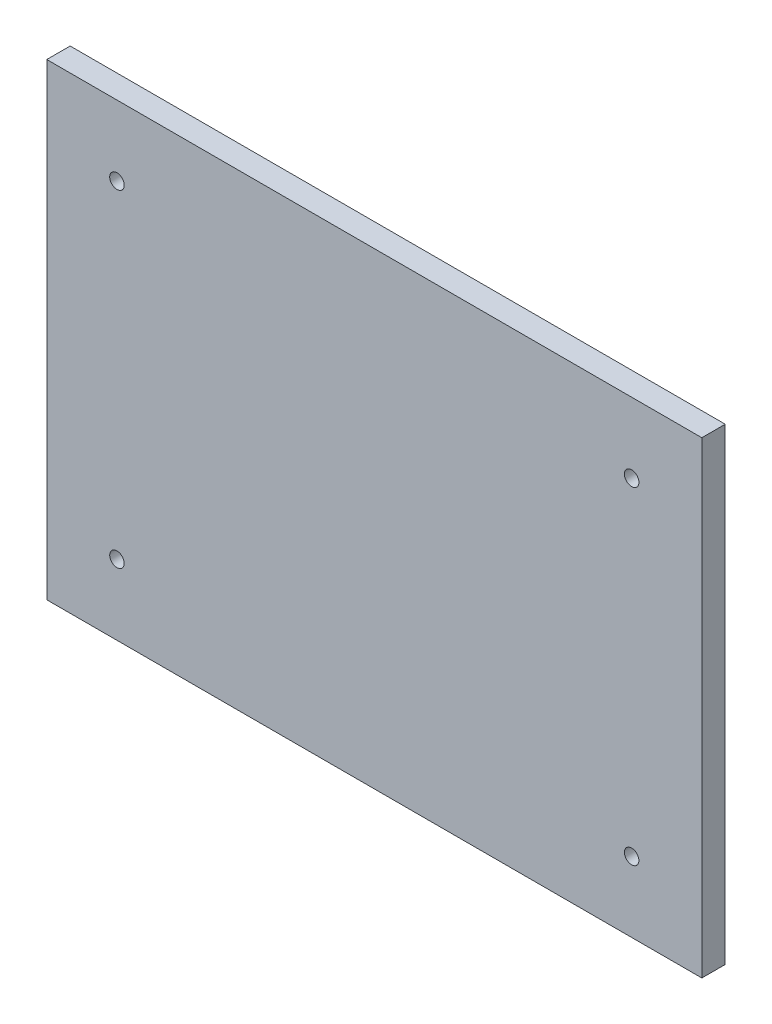
SolidWorks part; units mm, degrees
ref_plane "Plan de face" through (0, 0, 0) normal (0, 0, 1) x (1, 0, 0)
ref_plane "Plan de dessus" through (0, 0, 0) normal (0, 1, 0) x (1, 0, 0)
ref_plane "Plan de droite" through (0, 0, 0) normal (1, 0, 0) x (0, 0, -1)
sketch "Esquisse1" plane through (0, 0, 0) normal (0, 0, 1) x (1, 0, 0)
  line L0 (0, 0) -> (0, 37.8608) construction
  line L1 (-70, -50) -> (70, -50)
  line L2 (-70, -50) -> (-70, 50)
  line L3 (-70, 50) -> (70, 50)
  line L4 (70, -50) -> (70, 50)
  line L5 (-70, -50) -> (70, 50) construction
  line L6 (-70, 50) -> (70, -50) construction
  line L7 (0, 0) -> (30.7246, 0) construction
  circle A0 centre (-55, -35) radius 1.55
  circle A1 centre (55, -35) radius 1.55
  circle A2 centre (55, 35) radius 1.55
  circle A3 centre (-55, 35) radius 1.55
  point P0 (0, 0)
  dimension "D3" = 3.1
  dimension "D1" = 140
  dimension "D2" = 100
  dimension "D4" = 15
  dimension "D5" = 15
extrude "Boss.-Extru.1" add sketch "Esquisse1" against normal blind 5
